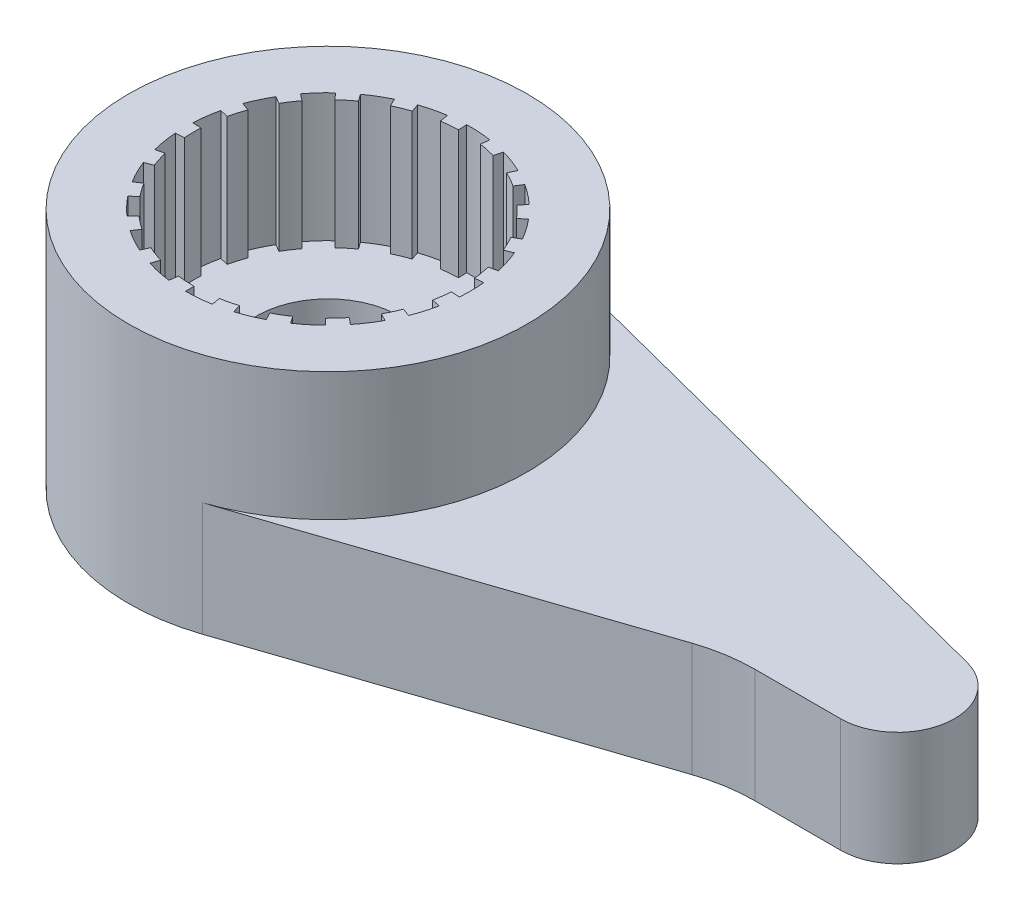
SolidWorks part; units mm, degrees
material "Nylon 6/10"
ref_plane "Front plane" through (0, 0, 0) normal (0, 0, 1) x (1, 0, 0)
ref_plane "Top plane" through (0, 0, 0) normal (0, 1, 0) x (1, 0, 0)
ref_plane "Right Plane" through (0, 0, 0) normal (1, 0, 0) x (0, 0, -1)
sketch "Sketch1" plane through (0, 0, 0) normal (0, 1, 0) x (1, 0, 0)
  circle A0 centre (0, 0) radius 2.5
  circle A1 centre (0, 0) radius 3.5
  dimension "D1" = 5
  dimension "D2" = 7
extrude "Boss-Extrude1" add sketch "Sketch1" along normal blind 2.25
sketch "Sketch6" plane through (0, 0, 0) normal (0, -1, 0) x (1, 0, 0)
  line L0 (0.4341, 2.462) -> (0.4081, 2.3143)
  line L1 (0.6927, 2.2456) -> (0.7369, 2.3889)
  line L2 (0, 2.35) -> (0, 0) construction
  line L3 (0, 0) -> (0.6927, 2.2456) construction
  line L4 (0, 0) -> (0.4081, 2.3143) construction
  line L5 (1.1405, 2.2247) -> (1.0721, 2.0912)
  line L6 (1.3238, 1.9417) -> (1.4083, 2.0656)
  line L7 (1.7456, 1.7897) -> (1.6409, 1.6823)
  line L8 (1.8373, 1.4652) -> (1.9546, 1.5587)
  line L9 (2.1956, 1.1956) -> (2.0638, 1.1239)
  line L10 (2.1876, 0.8586) -> (2.3272, 0.9134)
  line L11 (2.4504, 0.4954) -> (2.3034, 0.4656)
  line L12 (2.3434, 0.1756) -> (2.493, 0.1868)
  line L13 (2.4876, -0.2489) -> (2.3383, -0.234)
  line L14 (2.2911, -0.5229) -> (2.4373, -0.5563)
  line L15 (2.3037, -0.9711) -> (2.1655, -0.9128)
  line L16 (2.0352, -1.175) -> (2.1651, -1.25)
  line L17 (1.9151, -1.607) -> (1.8002, -1.5106)
  line L18 (1.5984, -1.7227) -> (1.7004, -1.8326)
  line L19 (1.3564, -2.1001) -> (1.275, -1.9741)
  line L20 (1.0196, -2.1173) -> (1.0847, -2.2524)
  line L21 (0.6771, -2.4066) -> (0.6365, -2.2622)
  line L22 (0.3502, -2.3238) -> (0.3726, -2.4721)
  line L23 (-0.0623, -2.4992) -> (-0.0586, -2.3493)
  line L24 (-0.3502, -2.3238) -> (-0.3726, -2.4721)
  line L25 (-0.7962, -2.3698) -> (-0.7484, -2.2276)
  line L26 (-1.0196, -2.1173) -> (-1.0847, -2.2524)
  line L27 (-1.4594, -2.0298) -> (-1.3718, -1.9081)
  line L28 (-1.5984, -1.7227) -> (-1.7004, -1.8326)
  line L29 (-1.9928, -1.5095) -> (-1.8733, -1.4189)
  line L30 (-2.0352, -1.175) -> (-2.1651, -1.25)
  line L31 (-2.3492, -0.8551) -> (-2.2083, -0.8037)
  line L32 (-2.2911, -0.5229) -> (-2.4373, -0.5563)
  line L33 (-2.4969, -0.1246) -> (-2.3471, -0.1171)
  line L34 (-2.3434, 0.1756) -> (-2.493, 0.1868)
  line L35 (-2.4227, 0.6169) -> (-2.2773, 0.5799)
  line L36 (-2.1876, 0.8586) -> (-2.3272, 0.9134)
  line L37 (-2.1332, 1.3036) -> (-2.0052, 1.2254)
  line L38 (-1.8373, 1.4652) -> (-1.9546, 1.5587)
  line L39 (-1.6542, 1.8745) -> (-1.555, 1.762)
  line L40 (-1.3238, 1.9417) -> (-1.4083, 2.0656)
  line L41 (-1.0282, 2.2788) -> (-0.9665, 2.142)
  line L42 (-0.6927, 2.2456) -> (-0.7369, 2.3889)
  line L43 (-0.3109, 2.4806) -> (-0.2922, 2.3318)
  line L44 (0, 2.35) -> (0, 2.5)
  arc A0 (0.6927, 2.2456) -> (0.4081, 2.3143) centre (0, 0) ccw
  circle A1 centre (0, 0) radius 2.5 construction
  arc A3 (0.7369, 2.3889) -> (0.4341, 2.462) centre (0, 0) ccw
  arc A4 (0.4081, 2.3143) -> (0, 2.35) centre (0, 0) ccw construction
  arc A5 (1.4083, 2.0656) -> (1.1405, 2.2247) centre (0, 0) ccw
  arc A6 (1.3238, 1.9417) -> (1.0721, 2.0912) centre (0, 0) ccw
  arc A7 (1.9546, 1.5587) -> (1.7456, 1.7897) centre (0, 0) ccw
  arc A8 (1.8373, 1.4652) -> (1.6409, 1.6823) centre (0, 0) ccw
  arc A9 (2.3272, 0.9134) -> (2.1956, 1.1956) centre (0, 0) ccw
  arc A10 (2.1876, 0.8586) -> (2.0638, 1.1239) centre (0, 0) ccw
  arc A11 (2.493, 0.1868) -> (2.4504, 0.4954) centre (0, 0) ccw
  arc A12 (2.3434, 0.1756) -> (2.3034, 0.4656) centre (0, 0) ccw
  arc A13 (2.4373, -0.5563) -> (2.4876, -0.2489) centre (0, 0) ccw
  arc A14 (2.2911, -0.5229) -> (2.3383, -0.234) centre (0, 0) ccw
  arc A15 (2.1651, -1.25) -> (2.3037, -0.9711) centre (0, 0) ccw
  arc A16 (2.0352, -1.175) -> (2.1655, -0.9128) centre (0, 0) ccw
  arc A17 (1.7004, -1.8326) -> (1.9151, -1.607) centre (0, 0) ccw
  arc A18 (1.5984, -1.7227) -> (1.8002, -1.5106) centre (0, 0) ccw
  arc A19 (1.0847, -2.2524) -> (1.3564, -2.1001) centre (0, 0) ccw
  arc A20 (1.0196, -2.1173) -> (1.275, -1.9741) centre (0, 0) ccw
  arc A21 (0.3726, -2.4721) -> (0.6771, -2.4066) centre (0, 0) ccw
  arc A22 (0.3502, -2.3238) -> (0.6365, -2.2622) centre (0, 0) ccw
  arc A23 (-0.3726, -2.4721) -> (-0.0623, -2.4992) centre (0, 0) ccw
  arc A24 (-0.3502, -2.3238) -> (-0.0586, -2.3493) centre (0, 0) ccw
  arc A25 (-1.0847, -2.2524) -> (-0.7962, -2.3698) centre (0, 0) ccw
  arc A26 (-1.0196, -2.1173) -> (-0.7484, -2.2276) centre (0, 0) ccw
  arc A27 (-1.7004, -1.8326) -> (-1.4594, -2.0298) centre (0, 0) ccw
  arc A28 (-1.5984, -1.7227) -> (-1.3718, -1.9081) centre (0, 0) ccw
  arc A29 (-2.1651, -1.25) -> (-1.9928, -1.5095) centre (0, 0) ccw
  arc A30 (-2.0352, -1.175) -> (-1.8733, -1.4189) centre (0, 0) ccw
  arc A31 (-2.4373, -0.5563) -> (-2.3492, -0.8551) centre (0, 0) ccw
  arc A32 (-2.2911, -0.5229) -> (-2.2083, -0.8037) centre (0, 0) ccw
  arc A33 (-2.493, 0.1868) -> (-2.4969, -0.1246) centre (0, 0) ccw
  arc A34 (-2.3434, 0.1756) -> (-2.3471, -0.1171) centre (0, 0) ccw
  arc A35 (-2.3272, 0.9134) -> (-2.4227, 0.6169) centre (0, 0) ccw
  arc A36 (-2.1876, 0.8586) -> (-2.2773, 0.5799) centre (0, 0) ccw
  arc A37 (-1.9546, 1.5587) -> (-2.1332, 1.3036) centre (0, 0) ccw
  arc A38 (-1.8373, 1.4652) -> (-2.0052, 1.2254) centre (0, 0) ccw
  arc A39 (-1.4083, 2.0656) -> (-1.6542, 1.8745) centre (0, 0) ccw
  arc A40 (-1.3238, 1.9417) -> (-1.555, 1.762) centre (0, 0) ccw
  arc A41 (-0.7369, 2.3889) -> (-1.0282, 2.2788) centre (0, 0) ccw
  arc A42 (-0.6927, 2.2456) -> (-0.9665, 2.142) centre (0, 0) ccw
  arc A43 (0, 2.5) -> (-0.3109, 2.4806) centre (0, 0) ccw
  arc A44 (0, 2.35) -> (-0.2922, 2.3318) centre (0, 0) ccw
  dimension "D1" = 0.15
  dimension "D2" = 17.143
  dimension "D3" = 10
  dimension "D4" = 21
extrude "Boss-Extrude4" add sketch "Sketch6" against normal up to surface (2.25 mm away) up to face at (0, 2.25, 3.5)
sketch "Sketch2" plane through (0, 0, 0) normal (0, 1, 0) x (1, 0, 0)
  line L0 (10.25, 0.9682) -> (0.875, 3.3889)
  line L2 (0, 0) -> (10, 0) construction
  line L6 (1.1153, -3.3176) -> (7.5441, -1.1564)
  line L7 (8.5, -1) -> (10, -1)
  circle A0 centre (0, 0) radius 3.5 construction
  arc A1 (1.1153, -3.3176) -> (0.875, 3.3889) centre (0, 0) ccw
  arc A2 (10, -1) -> (10.25, 0.9682) centre (10, 0) ccw
  arc A5 (7.5441, -1.1564) -> (8.5, -1) centre (8.5, -4) cw
  dimension "D1" = 10
  dimension "D2" = 1
  dimension "D3" = 3
  dimension "D4" = 1.5
extrude "Boss-Extrude2" add sketch "Sketch2" along normal blind 2 from offset 2.25 separate body
sketch "Sketch3" plane through (0, 2.25, 0) normal (0, 1, 0) x (1, 0, 0)
  circle A0 centre (0, 0) radius 1.25
  circle A3 centre (0, 0) radius 3.5
  circle A5 centre (0, 0) radius 3.5
  dimension "D2" = 2.5
  dimension "D1" = 0
extrude "Boss-Extrude3" add sketch "Sketch3" along normal up to vertex (2 mm away) up to point (0.875, 4.25, -3.3889)
sketch "Sketch4" plane through (0, 4.25, 0) normal (0, 1, 0) x (1, 0, 0)
  circle A0 centre (0, 0) radius 2.25
  dimension "D1" = 4.5
extrude "Cut-Extrude1" cut sketch "Sketch4" against normal blind 1.5
mirror "Mirror1" about plane through (10, 4.25, 0) normal (0, 1, 0) of bodies 105
delete or keep bodies "Body-Delete/Keep 1" type delete bodies bodies 105
